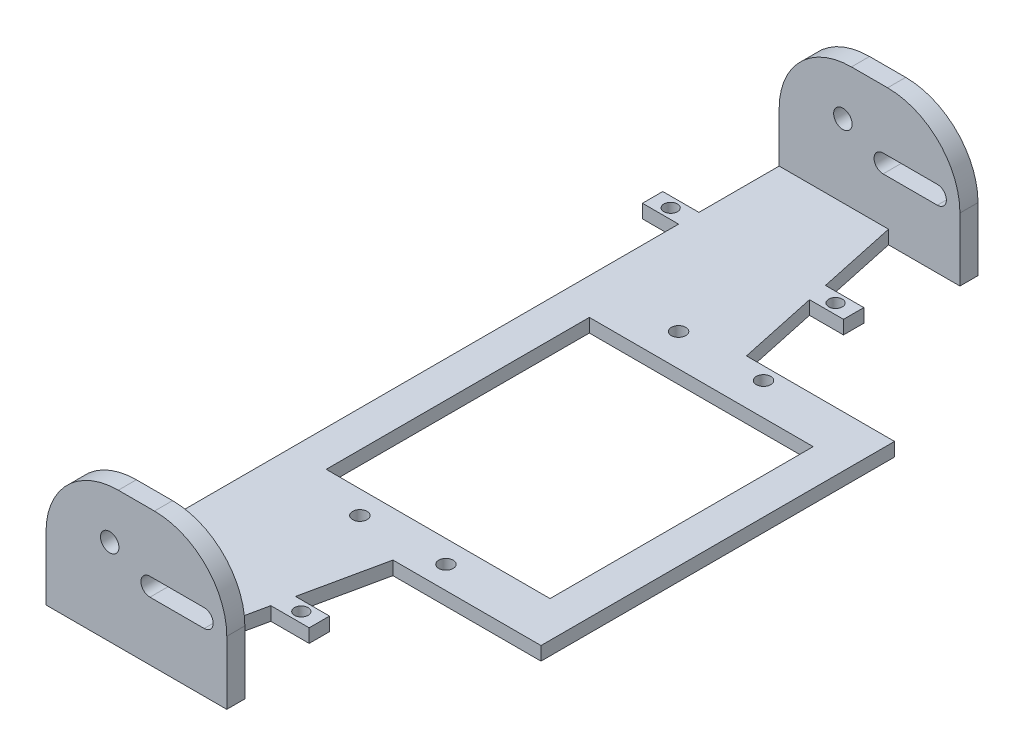
SolidWorks part; units mm, degrees
ref_plane "Front Plane" through (0, 0, 0) normal (0, 0, 1) x (1, 0, 0)
ref_plane "Top Plane" through (0, 0, 0) normal (0, 1, 0) x (1, 0, 0)
ref_plane "Right Plane" through (0, 0, 0) normal (1, 0, 0) x (0, 0, -1)
sketch "Sketch1" plane through (0, 0, 0) normal (0, 1, 0) x (1, 0, 0)
  line L0 (0, 39.1145) -> (0, -39.1145)
  line L1 (0, -39.1145) -> (65.532, -39.1145)
  line L2 (65.532, -39.1145) -> (65.532, 39.1145)
  line L3 (65.532, 39.1145) -> (0, 39.1145)
  line L4 (0, 39.1145) -> (0, 79.1145)
  line L5 (0, 79.1145) -> (24.2, 79.1145)
  line L6 (24.2, 79.1145) -> (32.766, 39.1145)
  line L7 (0, 39.1145) -> (32.766, 39.1145)
  line L8 (0, -39.1145) -> (0, -79.1145)
  line L9 (-8, 61.3645) -> (8, 61.3645)
  line L10 (-8, 61.3645) -> (-8, 56.8645)
  line L11 (-8, 56.8645) -> (8, 56.8645)
  line L12 (8, 61.3645) -> (8, 56.8645)
  line L13 (-55, 0) -> (55, 0) construction
  line L14 (8, 29.1145) -> (57.532, 29.1145)
  line L15 (20.483, 61.3645) -> (36.483, 61.3645)
  line L16 (20.483, 61.3645) -> (20.483, 56.8645)
  line L17 (20.483, 56.8645) -> (36.483, 56.8645)
  line L18 (36.483, 61.3645) -> (36.483, 56.8645)
  line L19 (8, 29.1145) -> (8, -29.1145)
  line L20 (8, -29.1145) -> (57.532, -29.1145)
  line L21 (0, -55) -> (0, 55) construction
  line L22 (0, -79.1145) -> (24.2, -79.1145)
  line L23 (24.2, -79.1145) -> (32.766, -39.1145)
  line L24 (32.766, -39.1145) -> (0, -39.1145)
  line L25 (57.532, 29.1145) -> (57.532, -29.1145)
  line L26 (20.483, -56.8645) -> (36.483, -56.8645)
  line L27 (20.483, -56.8645) -> (20.483, -61.3645)
  line L28 (20.483, -61.3645) -> (36.483, -61.3645)
  line L29 (36.483, -56.8645) -> (36.483, -61.3645)
  line L30 (8, 29.1145) -> (57.532, -29.1145) construction
  line L31 (8, -29.1145) -> (57.532, 29.1145) construction
  line L32 (-8, -56.8645) -> (8, -56.8645)
  line L33 (-8, -56.8645) -> (-8, -61.3645)
  line L34 (-8, -61.3645) -> (8, -61.3645)
  line L35 (8, -56.8645) -> (8, -61.3645)
  line L36 (0, 79.1145) -> (0, 81.1145)
  line L37 (0, 81.1145) -> (24.2, 81.1145)
  line L38 (24.2, 81.1145) -> (24.2, 79.1145)
  line L39 (0, -79.1145) -> (0, -81.0311)
  line L40 (0, -81.0311) -> (37.5753, -81.0311)
  line L41 (37.5753, -81.0311) -> (37.5753, -79.1145)
  line L42 (37.5753, -79.1145) -> (0, -79.1145)
  circle A0 centre (20.574, 36.2868) radius 1.6
  circle A1 centre (39.37, 36.2868) radius 1.5999
  circle A2 centre (20.574, -34.2415) radius 1.6
  circle A3 centre (39.4509, -34.0685) radius 1.5999
  circle A4 centre (-4, 59.1145) radius 1.5
  circle A5 centre (32.483, 59.1145) radius 1.5
  circle A6 centre (-4, -59.1145) radius 1.5
  circle A8 centre (32.483, -59.1145) radius 1.5
  point P8 (0, 59.1145)
  point P21 (28.483, 59.1145)
  point P30 (28.483, -59.1145)
  point P40 (0, -59.1145)
  point P47 (32.766, 0)
  dimension "D12" = 3
  dimension "D14" = 3
  dimension "D23" = 3
  dimension "D24" = 4
  dimension "D26" = 3
  dimension "D27" = 10
  dimension "D1" = 65.532
  dimension "D2" = 78.229
  dimension "D3" = 40
  dimension "D4" = 24.2
  dimension "D5" = 10
  dimension "D6" = 40
  dimension "D7" = 16
  dimension "D8" = 16
  dimension "D9" = 4.5
  dimension "D10" = 4.5
  dimension "D11" = 8
  dimension "D13" = 4
  dimension "D15" = 4
  dimension "D16" = 44.483
  dimension "D17" = 40
  dimension "D19" = 16
  dimension "D20" = 16
  dimension "D21" = 4.5
  dimension "D22" = 4.5
  dimension "D25" = 4
  dimension "D28" = 8
  dimension "D29" = 8
  dimension "D30" = 2.25
  dimension "D31" = 2.25
  dimension "D32" = 2.25
  dimension "D33" = 2.25
  dimension "D34" = 36.483
  dimension "D35" = 36.483
  dimension "D36" = 2
extrude "Boss-Extrude1" add sketch "Sketch1" along normal blind 3 contours L10 L11 L4 L9 A4 | L12 L9 L4 L11 | L17 L16 L15 L6 L5 L4 L9 L12 L11 L3 | L16 L17 L6 L15 | L18 L15 L6 L17 A5 | L2 L3 L0 L1 A3 A2 A1 A0 L14 L25 L20 L19 | L32 L35 L34 L8 L22 L23 L28 L27 L26 L1 | L27 L28 L23 L26 | L29 L26 L23 L28 A8 | L35 L32 L8 L34 | L33 L34 L8 L32 A6 region at (16.383, 0, -38.094) region at (14.3559, 0, -58.0459) region at (14.3559, 0, 58.0459) region at (-4, 0, -56.9563) region at (4, 0, -59.1145) region at (4, 0, 59.1145) region at (-0.0918, 0, 59.1145) region at (24.4878, 0, -59.0693) region at (28.5769, 0, -59.1346) region at (32.7239, 0, 56.9605) region at (24.4878, 0, 59.0693)
sketch "Sketch2" plane through (0, 0, 0) normal (0, 1, 0) x (1, 0, 0)
  line L0 (0, -79.1145) -> (0, -83.1145)
  line L1 (0, -1.65) -> (0, 1.65) construction
  line L2 (0, -79.1145) -> (24.2, -79.1145) construction
  line L3 (0, -83.1145) -> (40, -83.1145)
  line L4 (40, -83.1145) -> (40, -79.1145)
  line L5 (40, -79.1145) -> (0, -79.1145)
  line L6 (0, 79.1145) -> (40, 79.1145)
  line L7 (0, 79.1145) -> (24.2, 79.1145) construction
  line L8 (40, 79.1145) -> (40, 83.1145)
  line L9 (40, 83.1145) -> (0, 83.1145)
  line L10 (0, 83.1145) -> (0, 79.1145)
  dimension "D1" = 4
  dimension "D2" = 40
  dimension "D3" = 4
  dimension "D4" = 40
extrude "Boss-Extrude2" add sketch "Sketch2" along normal blind 30
sketch "Sketch3" plane through (0, 0, 0) normal (0, 0, 1) x (1, 0, 0)
  line L0 (-8, 3) -> (0, 3) construction
  line L1 (0, 30) -> (0, 0) construction
  circle A0 centre (14.1, 19.1) radius 2.0407
  dimension "D1" = 16.1
  dimension "D2" = 14.1
extrude "Cut-Extrude1" cut sketch "Sketch3" against normal through all both and the other way through all contours A0
sketch "Sketch4" plane through (0, 0, 83.1145) normal (0, 0, 1) x (1, 0, 0)
  line L0 (23, 17) -> (35, 17)
  line L1 (35, 17) -> (35, 13)
  line L2 (35, 13) -> (23, 13)
  line L3 (40, 30) -> (40, 0) construction
  line L4 (32.766, 3) -> (65.532, 3) construction
  circle A0 centre (23, 15) radius 2
  circle A1 centre (35, 15) radius 2
  point P12 (0, 0)
  dimension "D4" = 4
  dimension "D1" = 5
  dimension "D2" = 12
  dimension "D3" = 12
extrude "Cut-Extrude2" cut sketch "Sketch4" against normal through all both contours A1 L0 A0 L2 | A0 | L1 A1 | L1 A1 region at (29, 15, 83.1145) region at (23, 15, 83.1145) region at (35.8488, 15, 83.1145) region at (34.1512, 15, 83.1145)
fillet "Fillet1" radius 16 4 edges at (0, 30, -81.1145) (40, 30, -81.1145) (40, 30, 81.1145) (0, 30, 81.1145)
